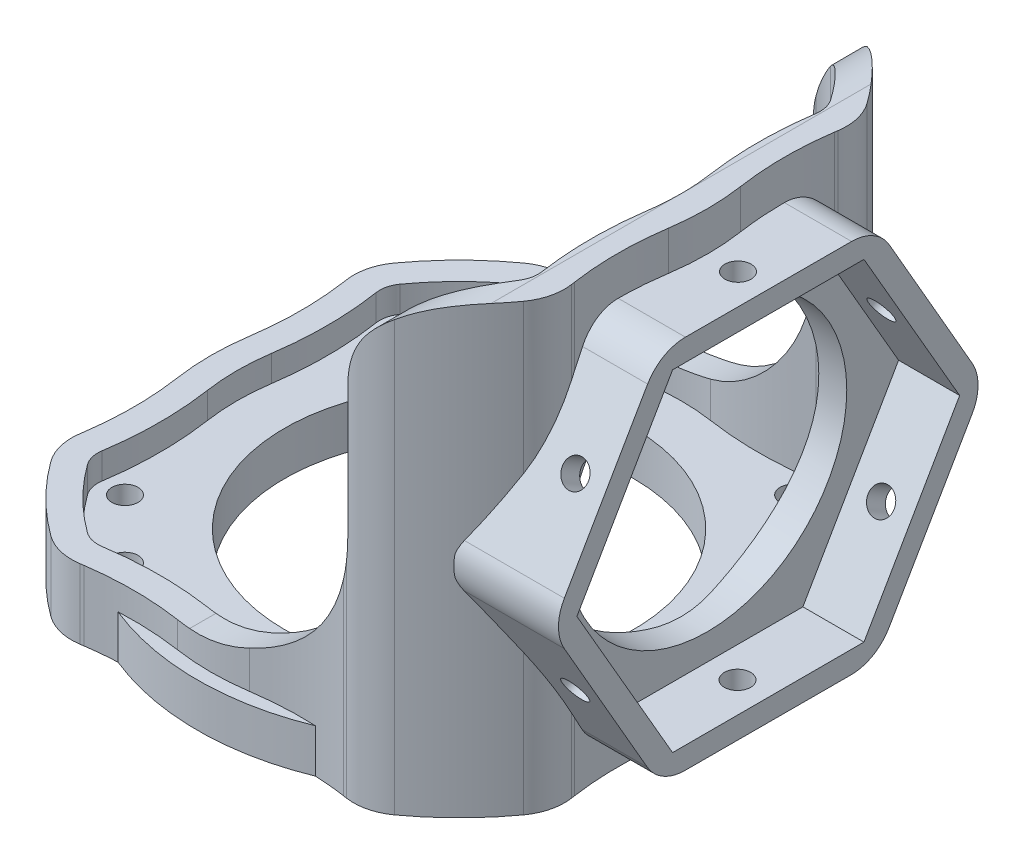
SolidWorks part; units mm, degrees
ref_plane "前视基准面" through (0, 0, 0) normal (0, 0, 1) x (1, 0, 0)
ref_plane "上视基准面" through (0, 0, 0) normal (0, 1, 0) x (1, 0, 0)
ref_plane "右视基准面" through (0, 0, 0) normal (1, 0, 0) x (0, 0, -1)
sketch "草图1" plane through (0, 0, 0) normal (0, 1, 0) x (1, 0, 0)
  line L0 (0, 0) -> (0, 46.6195) construction
  line L1 (0, 0) -> (-41.7463, 0) construction
  line L2 (-22.5267, 15.7734) -> (0, 0) construction
  line L3 (-15.7734, 22.5267) -> (0, 0) construction
  circle A0 centre (0, 0) radius 30
  circle A1 centre (0, 0) radius 20
  circle A2 centre (0, 0) radius 27.5 construction
  circle A3 centre (-22.5267, 15.7734) radius 1.5
  circle A4 centre (-15.7734, 22.5267) radius 1.5
  circle A5 centre (22.5267, 15.7734) radius 1.5
  circle A6 centre (15.7734, 22.5267) radius 1.5
  circle A7 centre (22.5267, -15.7734) radius 1.5
  circle A8 centre (15.7734, -22.5267) radius 1.5
  circle A9 centre (-22.5267, -15.7734) radius 1.5
  circle A10 centre (-15.7734, -22.5267) radius 1.5
  dimension "D1" = 60
  dimension "D2" = 40
  dimension "D3" = 55
  dimension "D5" = 3
  dimension "D4" = 35
  dimension "D6" = 35
extrude "凸台-拉伸1" add sketch "草图1" along normal blind 5
sketch "草图2" plane through (0, 5, 0) normal (0, 1, 0) x (1, 0, 0)
  line L0 (0, 0) -> (39.9587, 0) construction
  line L1 (0, 0) -> (0, -36.8515) construction
  line L2 (0, 0) -> (21.5668, 21.5668) construction
  arc A0 (24.7368, -3.2548) -> (24.949, 0.2177) centre (0, 0) ccw construction
  arc A1 (25.1774, -3.6784) -> (25.1774, 3.6784) centre (0.5, 0) ccw
  arc A2 (24.949, 0.2177) -> (24.6762, 3.686) centre (0, 0) ccw construction
  arc A3 (25.1774, 3.6784) -> (24.7671, 8.11) centre (64.7402, 9.5757) cw
  arc A4 (24.2388, 9.2464) -> (24.6762, 3.686) centre (64.2373, 9.5955) ccw construction
  arc A5 (24.7671, 8.11) -> (25.2125, 15.7044) centre (64.7402, 9.5757) cw
  arc A6 (24.7179, 15.7777) -> (24.2388, 9.2464) centre (64.2373, 9.5955) ccw construction
  arc A7 (25.2125, 15.7044) -> (24.675, 17.9275) centre (22.248, 16.1641) ccw
  arc A8 (24.7179, 15.7777) -> (24.2705, 17.6336) centre (22.248, 16.1641) ccw construction
  arc A9 (24.675, 17.9275) -> (17.9275, 24.675) centre (0, 0) ccw
  circle A10 centre (0, 0) radius 30 construction
  arc A11 (28.1446, 4.1207) -> (28.1446, -4.1207) centre (0.5, 0) cw
  arc A12 (28.1446, 4.1207) -> (28.1241, 14.8917) centre (64.7402, 9.5757) cw
  arc A13 (28.1241, 14.8917) -> (28.1806, 15.2677) centre (65.7457, 9.4297) cw
  arc A14 (28.1806, 15.2677) -> (27.1021, 19.6908) centre (22.248, 16.1641) ccw
  arc A15 (19.6908, 27.1021) -> (27.1021, 19.6908) centre (0, 0) cw
  arc A16 (15.2677, 28.1806) -> (19.6908, 27.1021) centre (16.1641, 22.248) cw
  arc A17 (14.8917, 28.1241) -> (15.2677, 28.1806) centre (9.4297, 65.7457) ccw
  arc A18 (4.1207, 28.1446) -> (14.8917, 28.1241) centre (9.5757, 64.7402) ccw
  arc A19 (4.1207, 28.1446) -> (-4.1207, 28.1446) centre (0, 0.5) ccw
  arc A20 (15.7044, 25.2125) -> (17.9275, 24.675) centre (16.1641, 22.248) cw
  arc A21 (8.11, 24.7671) -> (15.7044, 25.2125) centre (9.5757, 64.7402) ccw
  arc A22 (3.6784, 25.1774) -> (8.11, 24.7671) centre (9.5757, 64.7402) ccw
  arc A23 (-3.6784, 25.1774) -> (3.6784, 25.1774) centre (0, 0.5) cw
  arc A24 (-3.6784, 25.1774) -> (-8.11, 24.7671) centre (-9.5757, 64.7402) cw
  arc A25 (-8.11, 24.7671) -> (-15.7044, 25.2125) centre (-9.5757, 64.7402) cw
  arc A26 (-15.7044, 25.2125) -> (-17.9275, 24.675) centre (-16.1641, 22.248) ccw
  arc A27 (-4.1207, 28.1446) -> (-14.8917, 28.1241) centre (-9.5757, 64.7402) cw
  arc A28 (-14.8917, 28.1241) -> (-15.2677, 28.1806) centre (-9.4297, 65.7457) cw
  arc A29 (-15.2677, 28.1806) -> (-19.6908, 27.1021) centre (-16.1641, 22.248) ccw
  arc A30 (-19.6908, 27.1021) -> (-27.1021, 19.6908) centre (0, 0) ccw
  arc A31 (-28.1806, 15.2677) -> (-27.1021, 19.6908) centre (-22.248, 16.1641) cw
  arc A32 (-28.1241, 14.8917) -> (-28.1806, 15.2677) centre (-65.7457, 9.4297) ccw
  arc A33 (-28.1446, 4.1207) -> (-28.1241, 14.8917) centre (-64.7402, 9.5757) ccw
  arc A34 (-28.1446, 4.1207) -> (-28.1446, -4.1207) centre (-0.5, 0) ccw
  arc A35 (-24.675, 17.9275) -> (-17.9275, 24.675) centre (0, 0) cw
  arc A36 (-25.2125, 15.7044) -> (-24.675, 17.9275) centre (-22.248, 16.1641) cw
  arc A37 (-24.7671, 8.11) -> (-25.2125, 15.7044) centre (-64.7402, 9.5757) ccw
  arc A38 (-25.1774, 3.6784) -> (-24.7671, 8.11) centre (-64.7402, 9.5757) ccw
  arc A39 (-25.1774, -3.6784) -> (-25.1774, 3.6784) centre (-0.5, 0) cw
  arc A40 (-25.1774, -3.6784) -> (-24.7671, -8.11) centre (-64.7402, -9.5757) cw
  arc A41 (-24.7671, -8.11) -> (-25.2125, -15.7044) centre (-64.7402, -9.5757) cw
  arc A42 (-25.2125, -15.7044) -> (-24.675, -17.9275) centre (-22.248, -16.1641) ccw
  arc A43 (-24.675, -17.9275) -> (-17.9275, -24.675) centre (0, 0) ccw
  arc A44 (-28.1446, -4.1207) -> (-28.1241, -14.8917) centre (-64.7402, -9.5757) cw
  arc A45 (-28.1241, -14.8917) -> (-28.1806, -15.2677) centre (-65.7457, -9.4297) cw
  arc A46 (-28.1806, -15.2677) -> (-27.1021, -19.6908) centre (-22.248, -16.1641) ccw
  arc A47 (-19.6908, -27.1021) -> (-27.1021, -19.6908) centre (0, 0) cw
  arc A48 (-15.2677, -28.1806) -> (-19.6908, -27.1021) centre (-16.1641, -22.248) cw
  arc A49 (-14.8917, -28.1241) -> (-15.2677, -28.1806) centre (-9.4297, -65.7457) ccw
  arc A50 (-4.1207, -28.1446) -> (-14.8917, -28.1241) centre (-9.5757, -64.7402) ccw
  arc A51 (-15.7044, -25.2125) -> (-17.9275, -24.675) centre (-16.1641, -22.248) cw
  arc A52 (-8.11, -24.7671) -> (-15.7044, -25.2125) centre (-9.5757, -64.7402) ccw
  arc A53 (-3.6784, -25.1774) -> (-8.11, -24.7671) centre (-9.5757, -64.7402) ccw
  arc A54 (-3.6784, -25.1774) -> (3.6784, -25.1774) centre (0, -0.5) ccw
  arc A55 (3.6784, -25.1774) -> (8.11, -24.7671) centre (9.5757, -64.7402) cw
  arc A56 (8.11, -24.7671) -> (15.7044, -25.2125) centre (9.5757, -64.7402) cw
  arc A57 (15.7044, -25.2125) -> (17.9275, -24.675) centre (16.1641, -22.248) ccw
  arc A58 (4.1207, -28.1446) -> (-4.1207, -28.1446) centre (0, -0.5) cw
  arc A59 (4.1207, -28.1446) -> (14.8917, -28.1241) centre (9.5757, -64.7402) cw
  arc A60 (14.8917, -28.1241) -> (15.2677, -28.1806) centre (9.4297, -65.7457) cw
  arc A61 (15.2677, -28.1806) -> (19.6908, -27.1021) centre (16.1641, -22.248) ccw
  arc A62 (19.6908, -27.1021) -> (27.1021, -19.6908) centre (0, 0) ccw
  arc A63 (28.1806, -15.2677) -> (27.1021, -19.6908) centre (22.248, -16.1641) cw
  arc A64 (28.1241, -14.8917) -> (28.1806, -15.2677) centre (65.7457, -9.4297) ccw
  arc A65 (28.1446, -4.1207) -> (28.1241, -14.8917) centre (64.7402, -9.5757) ccw
  arc A66 (24.675, -17.9275) -> (17.9275, -24.675) centre (0, 0) cw
  arc A67 (25.2125, -15.7044) -> (24.675, -17.9275) centre (22.248, -16.1641) cw
  arc A68 (24.7671, -8.11) -> (25.2125, -15.7044) centre (64.7402, -9.5757) ccw
  arc A69 (25.1774, -3.6784) -> (24.7671, -8.11) centre (64.7402, -9.5757) ccw
  point P7 (24.95, 0)
  point P9 (25.45, 0)
  point P13 (0, -24.95)
  point P60 (0, 25.45)
  point P61 (0, 24.95)
  point P85 (-25.45, 0)
  point P86 (-24.95, 0)
  point P129 (0, -25.45)
  dimension "D2" = 30.5
  dimension "D1" = 0.5
extrude "凸台-拉伸2" add sketch "草图2" along normal blind 46 and the other way blind 5
sketch "草图3" plane through (0, 0, 0) normal (0, 0, 1) x (1, 0, 0)
  line L0 (-30.7273, 8) -> (-30.7273, -1.7514)
  line L2 (-30.7273, -1.7514) -> (-34.3096, -1.7514)
  line L3 (-34.3096, -1.7514) -> (-34.3096, 55.8818)
  line L4 (-34.3096, 55.8818) -> (36.2257, 55.8818)
  line L5 (36.2257, 55.8818) -> (36.2257, -1.7514)
  line L6 (36.2257, -1.7514) -> (28.45, -1.7514)
  line L7 (28.45, -1.7514) -> (28.45, 51)
  line L8 (28.45, 5) -> (28.45, 51) construction
  line L9 (28.45, 51) -> (25.45, 51)
  line L10 (14.8917, 51) -> (4.1207, 51) construction
  line L11 (15.45, 41) -> (15.45, 26)
  line L12 (-2.55, 8) -> (-30.7273, 8)
  line L13 (-27.7815, 5) -> (-30, 5) construction
  arc A0 (15.45, 26) -> (-2.55, 8) centre (-2.55, 26) cw
  arc A1 (25.45, 51) -> (15.45, 41) centre (25.45, 41) ccw
  point P20 (15.45, 51)
  dimension "D1" = 18
  dimension "D2" = 10
  dimension "D3" = 3
  dimension "D4" = 3
extrude "切除-拉伸1" cut sketch "草图3" along normal through all and the other way through all
sketch "草图4" plane through (28.45, 0, 0) normal (1, 0, 0) x (0, 0, -1)
  line L0 (0, 0) -> (0, 56.7093) construction
  line L1 (28.1446, 5) -> (27.7402, 5) construction
  circle A2 centre (0, 25) radius 20 construction
  circle A3 centre (0, 25) radius 16
  dimension "D1" = 40
  dimension "D2" = 32
extrude "切除-拉伸2" cut sketch "草图4" against normal blind 22 and the other way blind 19
sketch "草图5" plane through (28.45, 0, 0) normal (1, 0, 0) x (0, 0, -1)
  line L1 (13.8308, 5.9813) -> (23.3793, 22.4685)
  line L2 (23.386, 27.4685) -> (13.882, 43.9813)
  line L3 (9.5553, 46.4871) -> (-9.4973, 46.5128)
  line L4 (-13.8308, 44.0187) -> (-23.3793, 27.5315)
  line L5 (-23.386, 22.5315) -> (-13.882, 6.0187)
  line L6 (-9.5553, 3.5129) -> (9.4973, 3.4872)
  circle A0 centre (0, 25) radius 16
  arc A1 (-4.1207, 40.4603) -> (-14.8917, 30.8513) centre (0, 25) ccw construction
  circle A2 centre (0, 25) radius 22.5 construction
  circle A3 centre (0, 25) radius 21.5 construction
  arc A4 (13.882, 43.9813) -> (9.5553, 46.4871) centre (9.5485, 41.4871) ccw
  arc A5 (23.3793, 22.4685) -> (23.386, 27.4685) centre (19.0525, 24.9743) ccw
  arc A6 (13.8308, 5.9813) -> (9.4973, 3.4872) centre (9.504, 8.4872) cw
  arc A7 (-13.882, 6.0187) -> (-9.5553, 3.5129) centre (-9.5485, 8.5129) ccw
  arc A8 (-23.3793, 27.5315) -> (-23.386, 22.5315) centre (-19.0525, 25.0257) ccw
  arc A9 (-9.4973, 46.5128) -> (-13.8308, 44.0187) centre (-9.504, 41.5128) ccw
  dimension "D1" = 45
  dimension "D2" = 43
  dimension "D3" = 5
sketch "草图7" plane through (0, 51, 0) normal (0, 1, 0) x (1, 0, 0)
  line L0 (28.1241, -14.8917) -> (31.1027, -14.0835)
  line L1 (31.1027, -14.0835) -> (31.1027, 14.2516)
  line L2 (31.1027, 14.2516) -> (28.1241, 14.8917)
  arc A0 (28.1241, -14.8917) -> (28.1446, -4.1207) centre (64.7402, -9.5757) cw
  arc A1 (28.1446, -4.1207) -> (28.1241, -14.8917) centre (64.7402, -9.5757) ccw construction
  arc A2 (28.1446, -4.1207) -> (28.1446, 4.1207) centre (0.5, 0) ccw
  arc A3 (28.1446, 4.1207) -> (28.1241, 14.8917) centre (64.7402, 9.5757) cw
extrude "切除-拉伸3" cut sketch "草图7" against normal through all
extrude "凸台-拉伸4" add sketch "草图5" along normal blind 7 and the other way blind 5
sketch "草图8" plane through (0, 51, 0) normal (0, 1, 0) x (1, 0, 0)
  line L0 (17.9275, -24.675) -> (17.9275, 24.675)
  arc A0 (17.9275, -24.675) -> (24.675, -17.9275) centre (0, 0) ccw
  arc A1 (24.675, -17.9275) -> (25.2125, -15.7044) centre (22.248, -16.1641) ccw
  arc A2 (25.2125, -15.7044) -> (25.1774, -3.6784) centre (64.7402, -9.5757) cw
  arc A3 (25.1774, -3.6784) -> (25.45, 0) centre (0.5, 0) ccw
  arc A4 (25.45, 0) -> (25.1774, 3.6784) centre (0.5, 0) ccw
  arc A5 (25.1774, 3.6784) -> (25.2125, 15.7044) centre (64.7403, 9.5757) cw
  arc A6 (25.2125, 15.7044) -> (24.675, 17.9275) centre (22.248, 16.1641) ccw
  arc A7 (24.675, 17.9275) -> (17.9275, 24.675) centre (0, 0) ccw
extrude "切除-拉伸4" cut sketch "草图8" against normal up to surface (46 mm away) up to face at (0, 5, 28.5061)
sketch "草图9" plane through (35.45, 0, 0) normal (1, 0, 0) x (0, 0, -1)
  line L1 (10.9697, 6) -> (21.9393, 25)
  line L2 (21.9393, 25) -> (10.9697, 44)
  line L3 (10.9697, 44) -> (-10.9697, 44)
  line L4 (-10.9697, 44) -> (-21.9393, 25)
  line L5 (-21.9393, 25) -> (-10.9697, 6)
  line L6 (-10.9697, 6) -> (10.9697, 6)
  circle A2 centre (0, 25) radius 19 construction
  dimension "D2" = 38
extrude "切除-拉伸5" cut sketch "草图9" against normal blind 7
sketch "草图10" plane through (0, 17.0543, 29.4472) normal (0, 0.5012, 0.8654) x (1, 0, 0)
  line L0 (35.45, 21.6338) -> (31.95, 21.6338) construction
  line L1 (35.45, 31.16) -> (35.45, 12.1075) construction
  circle A0 centre (31.95, 21.6338) radius 1.5
  circle A1 centre (31.95, 21.6338) radius 3 construction
  dimension "D2" = 3
  dimension "D3" = 6
  dimension "D1" = 3.5
sketch "草图11" plane through (0, -4.5041, 7.8256) normal (0, -0.4988, 0.8667) x (1, 0, 0)
  line L0 (35.45, 21.6675) -> (31.95, 21.6675) construction
  line L1 (35.45, 31.1937) -> (35.45, 12.1412) construction
  circle A0 centre (31.95, 21.6675) radius 1.5
  circle A1 centre (31.95, 21.6675) radius 3 construction
  dimension "D1" = 6
  dimension "D2" = 3
  dimension "D3" = 3.5
extrude "切除-拉伸6" cut sketch "草图10" against normal through all
extrude "切除-拉伸7" cut sketch "草图11" against normal through all
sketch "草图12" plane through (0, 3.5, -0.0047) normal (0, -1, 0.0013) x (1, 0, 0)
  line L0 (35.45, 0.0337) -> (31.95, 0.0337) construction
  line L1 (35.45, 9.56) -> (35.45, -9.4926) construction
  circle A0 centre (31.95, 0.0337) radius 1.5
  circle A1 centre (31.95, 0.0337) radius 3 construction
  dimension "D2" = 3
  dimension "D3" = 6
  dimension "D1" = 3.5
extrude "切除-拉伸8" cut sketch "草图12" against normal through all
sketch "草图13" plane through (0, 0, 0) normal (0, -1, 0) x (1, 0, 0)
  line L0 (-14.0904, 25.6743) -> (-15.604, 24.7943)
  line L1 (-15.604, 24.7943) -> (-17.3639, 24.0199)
  line L2 (-17.3639, 24.0199) -> (-20.8838, 20.4649)
  line L3 (-20.8838, 20.4649) -> (-23.9813, 16.8394)
  line L4 (-23.9813, 16.8394) -> (-26.0197, 14.4535)
  line L5 (-26.0197, 14.4535) -> (-25.5653, 18.6521)
  line L6 (-25.5653, 18.6521) -> (-20.8838, 24.1315)
  line L7 (-20.8838, 24.1315) -> (-17.2837, 26.2246)
  line L8 (-17.2837, 26.2246) -> (-14.0904, 25.6743)
  line L9 (-21.4676, -19.5744) -> (-18.6381, -22.3759)
  line L10 (-18.6381, -22.3759) -> (-16.3467, -24.3337)
  line L11 (-16.3467, -24.3337) -> (-15.3102, -25.612)
  line L12 (-15.3102, -25.612) -> (-16.3467, -26.4523)
  line L13 (-16.3467, -26.4523) -> (-20.653, -24.0308)
  line L14 (-20.653, -24.0308) -> (-24.3427, -20.1015)
  line L15 (-24.3427, -20.1015) -> (-25.7925, -17.6078)
  line L16 (-25.7925, -17.6078) -> (-26.0197, -15.2619)
  line L17 (-26.0197, -15.2619) -> (-25.0137, -15.4353)
  line L18 (-25.0137, -15.4353) -> (-23.3178, -17.8374)
  line L19 (-23.3178, -17.8374) -> (-21.4676, -19.5744)
  line L20 (23.7623, -17.4526) -> (24.8079, -16.1747)
  line L21 (24.8079, -16.1747) -> (25.9115, -15.6326)
  line L22 (25.9115, -15.6326) -> (26.2407, -17.1234)
  line L23 (26.2407, -17.1234) -> (25.0402, -19.4275)
  line L24 (25.0402, -19.4275) -> (22.5619, -22.0027)
  line L25 (22.5619, -22.0027) -> (19.2897, -24.4617)
  line L26 (19.2897, -24.4617) -> (16.7339, -25.9913)
  line L27 (16.7339, -25.9913) -> (14.7396, -25.7589)
  line L28 (14.7396, -25.7589) -> (15.3397, -24.6072)
  line L29 (15.3397, -24.6072) -> (16.9544, -24.0987)
  line L30 (16.9544, -24.0987) -> (18.775, -22.207)
  line L31 (18.775, -22.207) -> (22.5619, -18.9047)
  line L32 (22.5619, -18.9047) -> (23.7623, -17.4526)
  line L33 (14.9976, 25.5005) -> (16.9544, 24.4377)
  line L34 (16.9544, 24.4377) -> (19.002, 22.7487)
  line L35 (19.002, 22.7487) -> (20.71, 20.718)
  line L36 (20.71, 20.718) -> (22.5619, 19.01)
  line L37 (22.5619, 19.01) -> (24.0501, 16.8394)
  line L38 (24.0501, 16.8394) -> (25.8018, 15.2238)
  line L39 (25.8018, 15.2238) -> (26.0618, 16.5239)
  line L40 (26.0618, 16.5239) -> (24.2428, 19.2523)
  line L41 (24.2428, 19.2523) -> (22.3922, 21.4524)
  line L42 (22.3922, 21.4524) -> (19.856, 23.7916)
  line L43 (19.856, 23.7916) -> (17.8147, 25.6743)
  line L44 (17.8147, 25.6743) -> (15.976, 26.2246)
  line L45 (15.976, 26.2246) -> (14.9976, 25.5005)
extrude "凸台-拉伸5" add sketch "草图13" against normal up to surface (5 mm away) up to face at (0, 5, 20)
